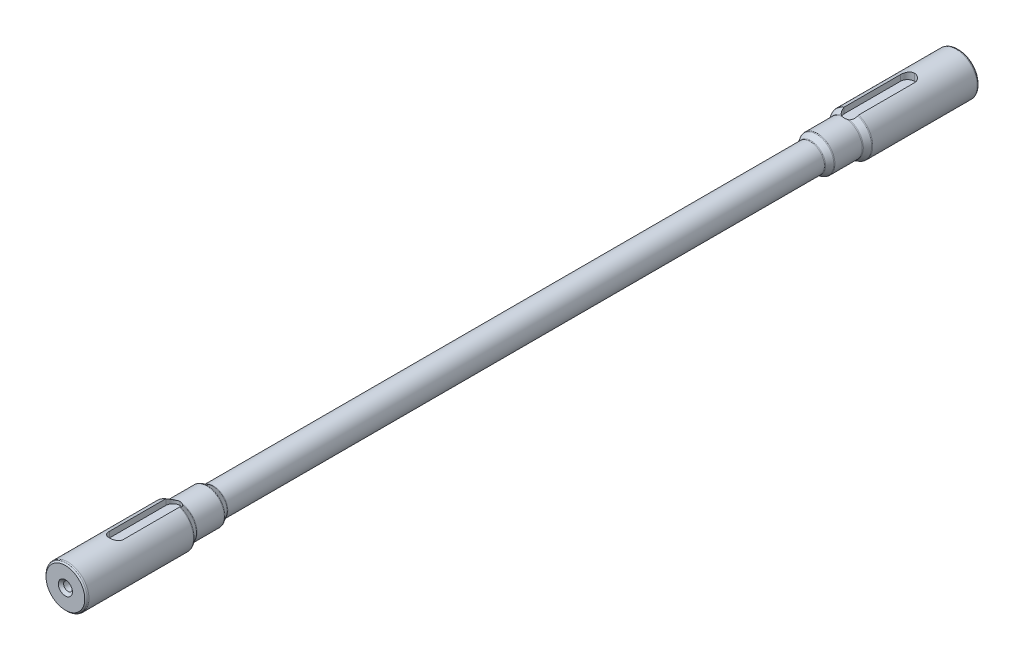
SolidWorks part; units mm, degrees
material "1.2210 (115CrV3)"
ref_plane "Front Plane" through (0, 0, 0) normal (0, 0, 1) x (1, 0, 0)
ref_plane "Top Plane" through (0, 0, 0) normal (0, 1, 0) x (1, 0, 0)
ref_plane "Right Plane" through (0, 0, 0) normal (1, 0, 0) x (0, 0, -1)
sketch "Sketch1" plane through (0, 0, 0) normal (0, 0, 1) x (1, 0, 0)
  circle A0 centre (0, 0) radius 12
  dimension "D1" = 24
extrude "Boss-Extrude1" add sketch "Sketch1" along normal mid plane 507
sketch "Sketch2" plane through (0, 0, 0) normal (0, 1, 0) x (1, 0, 0)
  line L0 (-10, 173.0359) -> (-8, 169.5718)
  line L1 (-12, 253.5) -> (-12, -253.5) construction
  line L2 (-8, 169.5718) -> (-8, -169.5718)
  line L3 (-12, 176.5) -> (-12, -176.5)
  line L4 (0, 0) -> (-12, 0) construction
  line L5 (0, 0) -> (0, 182.5339) construction
  line L6 (-10, -173.0359) -> (-8, -169.5718)
  line L7 (12, 253.5) -> (-12, 253.5) construction
  line L8 (-10, 173.0359) -> (-10, 189.0359)
  line L9 (-10, 189.0359) -> (-12, 192.5)
  line L10 (-12, 192.5) -> (-12, 176.5)
  line L11 (-12, -192.5) -> (-12, -176.5)
  line L12 (-10, -173.0359) -> (-10, -189.0359)
  line L13 (-10, -189.0359) -> (-12, -192.5)
  point P10 (-8, 0)
  dimension "D1" = 30
  dimension "D2" = 16
  dimension "D3" = 77
  dimension "D4" = 20
  dimension "D5" = 16
revolve "Cut-Revolve1" cut sketch "Sketch2" angle 360 about L5
chamfer "Chamfer1" distance 1 angle 45 2 edges at (12, 0, 253.5) (12, 0, -253.5)
fillet "Fillet1" radius 1 10 edges at (8, 0, -169.5718) (8, 0, 169.5718) (12, 0, -252.5) (12, 0, 252.5) (10, 0, -173.0359) (10, 0, -189.0359) (12, 0, 192.5) (10, 0, 189.0359) (12, 0, -192.5) (10, 0, 173.0359)
sketch "Sketch3" plane through (0, 0, 0) normal (1, 0, 0) x (0, 0, -1)
  line L1 (228.5, 16) -> (188.5, 16)
  line L2 (228.5, 16) -> (228.5, 8)
  line L3 (228.5, 8) -> (188.5, 8)
  line L4 (188.5, 16) -> (188.5, 8)
  line L5 (228.5, 16) -> (188.5, 8) construction
  line L6 (228.5, 8) -> (188.5, 16) construction
  line L7 (0, 0) -> (0, -38.9034) construction
  line L8 (-228.5, 8) -> (-188.5, 16) construction
  line L9 (-228.5, 16) -> (-188.5, 8) construction
  line L10 (-188.5, 16) -> (-188.5, 8)
  line L11 (-228.5, 8) -> (-188.5, 8)
  line L12 (-228.5, 16) -> (-228.5, 8)
  line L13 (-228.5, 16) -> (-188.5, 16)
  line L14 (252.0858, 12) -> (192.7679, 12) construction
  line L15 (253.5, -11) -> (253.5, 11) construction
  point P0 (208.5, 12)
  point P14 (-208.5, 12)
  dimension "D1" = 8
  dimension "D2" = 40
  dimension "D3" = 25
extrude "Cut-Extrude1" cut sketch "Sketch3" against normal mid plane 8
fillet "Fillet2" radius 4 8 edges at (-4, 8.5826, 188.5) (4, 8.5826, 188.5) (4, 9.6569, 228.5) (-4, 9.6569, 228.5) (-4, 8.5826, -188.5) (4, 8.5826, -188.5) (-4, 9.6569, -228.5) (4, 9.6569, -228.5)
hole_wizard "M6 Tapped Hole1" positions "Sketch5" profile "Sketch4" tap size "M6" standard "ISO"
sketch "Sketch5" plane through (0, 0, -253.5) normal (0, 0, -1) x (-1, 0, 0)
  point P0 (0, 0)
sketch "Sketch4" plane through (0, 0, -253.5) normal (1, 0, 0) x (0, 1, 0)
  line L0 (0, 0) -> (0, 18.5022)
  line L1 (0, 18.5022) -> (2.5, 17)
  line L2 (2.5, 17) -> (2.5, 1.5)
  line L3 (2.5, 1.5) -> (4, 0)
  line L5 (4, 0) -> (0, 0)
  line L6 (-2.5, 1.5) -> (-4, 0) construction
  line L10 (0, 18.5022) -> (-2.5, 17) construction
  line L11 (0, -6.35) -> (0, 107.95) construction
  dimension "Tap Drill Dia." = 5
  dimension "Tap Drill Depth" = 17
  dimension "Near C'Sink Dia." = 8
  dimension "Near C'Sink Angle" = 90
  dimension "Drill Angle" = 118
hole_wizard "M6 Tapped Hole2" positions "Sketch7" profile "Sketch6" tap size "M6" standard "ISO"
sketch "Sketch7" plane through (0, 0, 253.5) normal (0, 0, 1) x (1, 0, 0)
  point P0 (0, 0)
sketch "Sketch6" plane through (0, 0, 253.5) normal (1, 0, 0) x (0, -1, 0)
  line L0 (0, 0) -> (0, 18.5022)
  line L1 (0, 18.5022) -> (2.5, 17)
  line L2 (2.5, 17) -> (2.5, 1.5)
  line L3 (2.5, 1.5) -> (4, 0)
  line L5 (4, 0) -> (0, 0)
  line L6 (-2.5, 1.5) -> (-4, 0) construction
  line L10 (0, 18.5022) -> (-2.5, 17) construction
  line L11 (0, -6.35) -> (0, 107.95) construction
  dimension "Tap Drill Dia." = 5
  dimension "Tap Drill Depth" = 17
  dimension "Near C'Sink Dia." = 8
  dimension "Near C'Sink Angle" = 90
  dimension "Drill Angle" = 118
